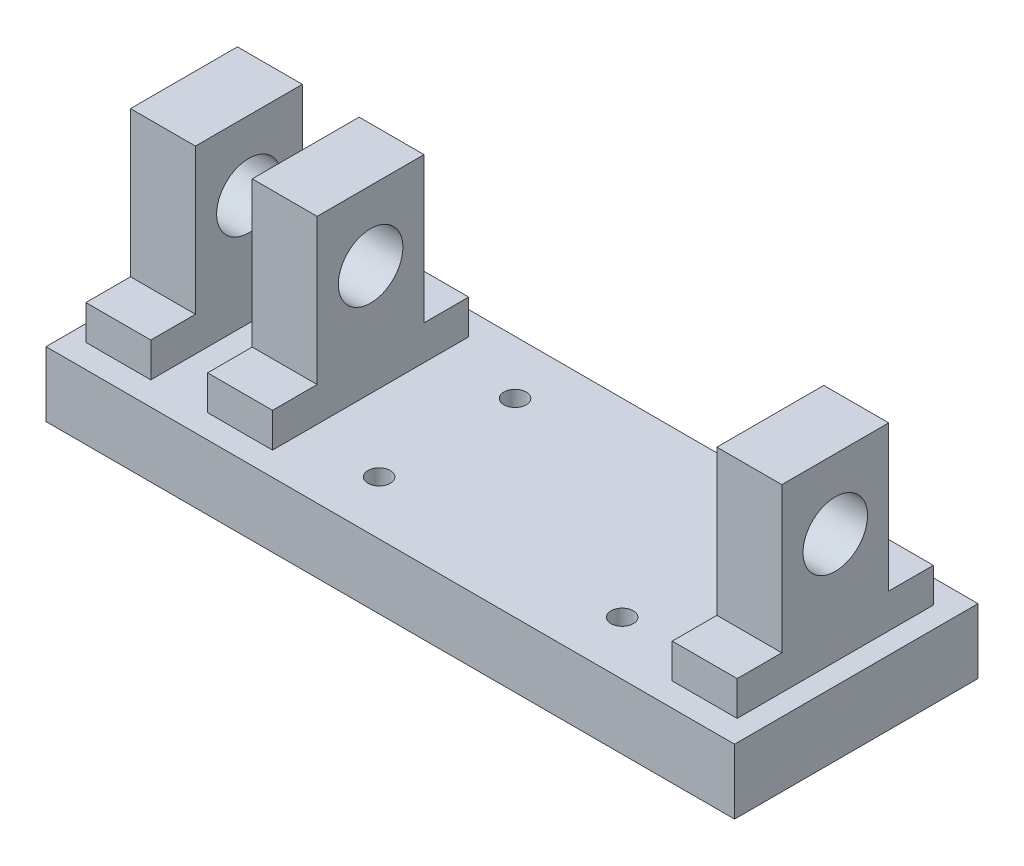
SolidWorks part; units mm, degrees
note: The reader was unsure of these and kept them because the rebuilt part matched: shared geometry of "Sketch2<3>".
ref_plane "Front Plane" through (0, 0, 0) normal (0, 0, 1) x (1, 0, 0)
ref_plane "Top Plane" through (0, 0, 0) normal (0, 1, 0) x (1, 0, 0)
ref_plane "Right Plane" through (0, 0, 0) normal (1, 0, 0) x (0, 0, -1)
sketch "Sketch1" plane through (0, 0, 0) normal (0, 1, 0) x (1, 0, 0)
  line L0 (-18.75, -16.75) -> (46.65, -16.75) construction
  line L1 (-84.85, -30) -> (84.85, -30)
  line L2 (-84.85, -30) -> (-84.85, 30)
  line L3 (-84.85, 30) -> (84.85, 30)
  line L4 (84.85, -30) -> (84.85, 30)
  line L5 (-84.85, -30) -> (84.85, 30) construction
  line L6 (-84.85, 30) -> (84.85, -30) construction
  line L7 (-16, -16.75) -> (43.9, -16.75) construction
  line L8 (-16, -16.75) -> (-16, 16.75) construction
  line L9 (-16, 16.75) -> (43.9, 16.75) construction
  line L10 (43.9, -16.75) -> (43.9, 16.75) construction
  line L11 (43.9, 19.5) -> (43.9, -19.5) construction
  circle A0 centre (-16, -16.75) radius 2.75
  circle A1 centre (43.9, -16.75) radius 2.75
  circle A2 centre (43.9, 16.75) radius 2.75
  circle A3 centre (-16, 16.75) radius 2.75
  point P0 (0, 0)
  point P18 (43.9, 0)
  dimension "D2" = 5.5
  dimension "D1" = 60
  dimension "D3" = 65.4
  dimension "D4" = 39
  dimension "D5" = 38.2
  dimension "D6" = 66.1
extrude "Boss-Extrude1" add sketch "Sketch1" along normal blind 16
sketch "Sketch2" plane through (84.85, 0, 0) normal (1, 0, 0) x (0, 0, -1)
  line L0 (-30, 16) -> (30, 16) construction
  line L1 (-24.175, 16) -> (24.175, 16)
  line L2 (-24.175, 16) -> (-24.175, 24.5)
  line L3 (-24.175, 24.5) -> (24.175, 24.5)
  line L4 (24.175, 16) -> (24.175, 24.5)
  line L5 (0, 51.2) -> (0, 60.4) construction
  line L6 (-13.175, 24.5) -> (13.175, 24.5)
  line L7 (-13.175, 24.5) -> (-13.175, 60.4)
  line L8 (-13.175, 60.4) -> (13.175, 60.4)
  line L9 (13.175, 24.5) -> (13.175, 60.4)
  circle A0 centre (0, 43.25) radius 7.95
  point P11 (0, 60.4)
  point P12 (0, 24.5)
  point P13 (0, 16)
  dimension "D4" = 15.9
  dimension "D1" = 44.4
  dimension "D2" = 8.5
  dimension "D3" = 9.2
  dimension "D5" = 48.35
  dimension "D6" = 26.35
extrude "Boss-Extrude2" add sketch "Sketch2" against normal blind 16 from offset 5.18 offset against normal yes
ref_plane "Plane1" through (-80.85, 0, 0) normal (-1, 0, 0) x (0, 0, 1)
extrude "Boss-Extrude3" add sketch "Sketch2<3>" along normal blind 16 from surface at -165.7
sketch "Sketch2<3>" plane through (84.85, 0, 0) normal (1, 0, 0) x (0, 0, -1) same geometry as "Sketch2"
pattern_linear "LPattern1" count 2 spacing 30 along (1, 0, 0) of "Boss-Extrude3"
